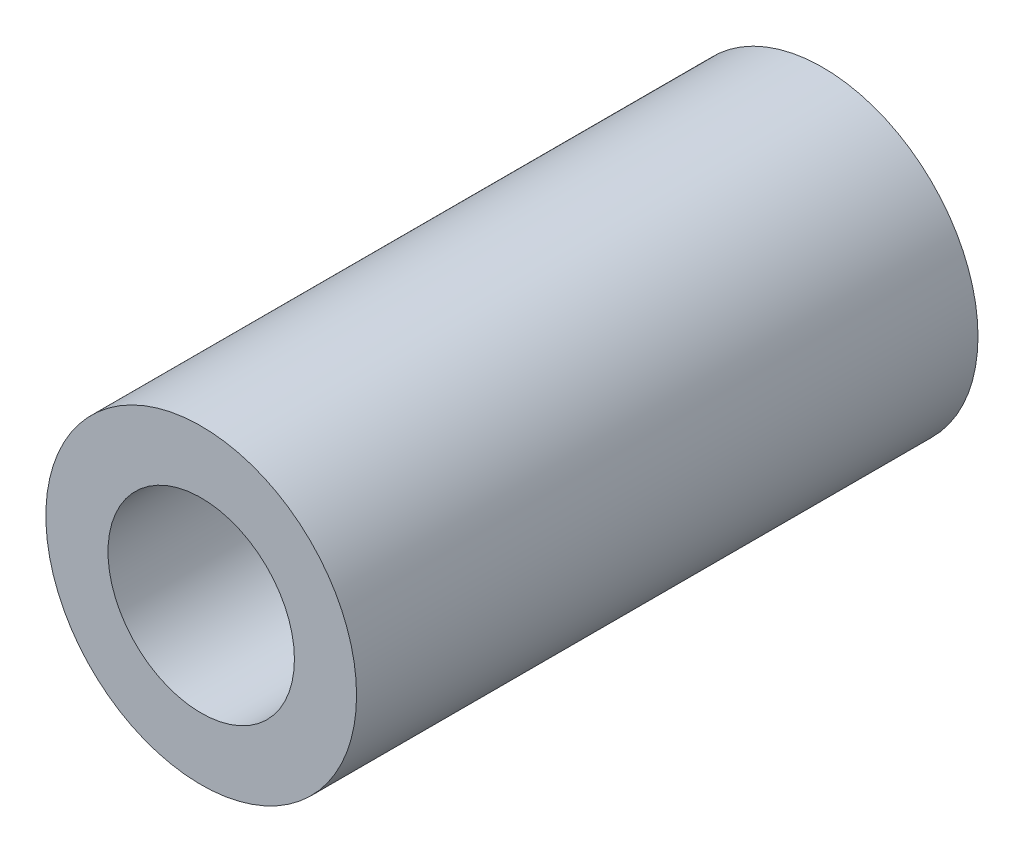
SolidWorks part; units mm, degrees
ref_plane "Front Plane" through (0, 0, 0) normal (0, 0, 1) x (1, 0, 0)
ref_plane "Top Plane" through (0, 0, 0) normal (0, 1, 0) x (1, 0, 0)
ref_plane "Right Plane" through (0, 0, 0) normal (1, 0, 0) x (0, 0, -1)
sketch "Sketch1" plane through (0, 0, 0) normal (0, 0, 1) x (1, 0, 0)
  circle A0 centre (0, 0) radius 5
  circle A1 centre (0, 0) radius 3
  dimension "D1" = 6
  dimension "D2" = 10
extrude "Boss-Extrude1" add sketch "Sketch1" along normal blind 20
